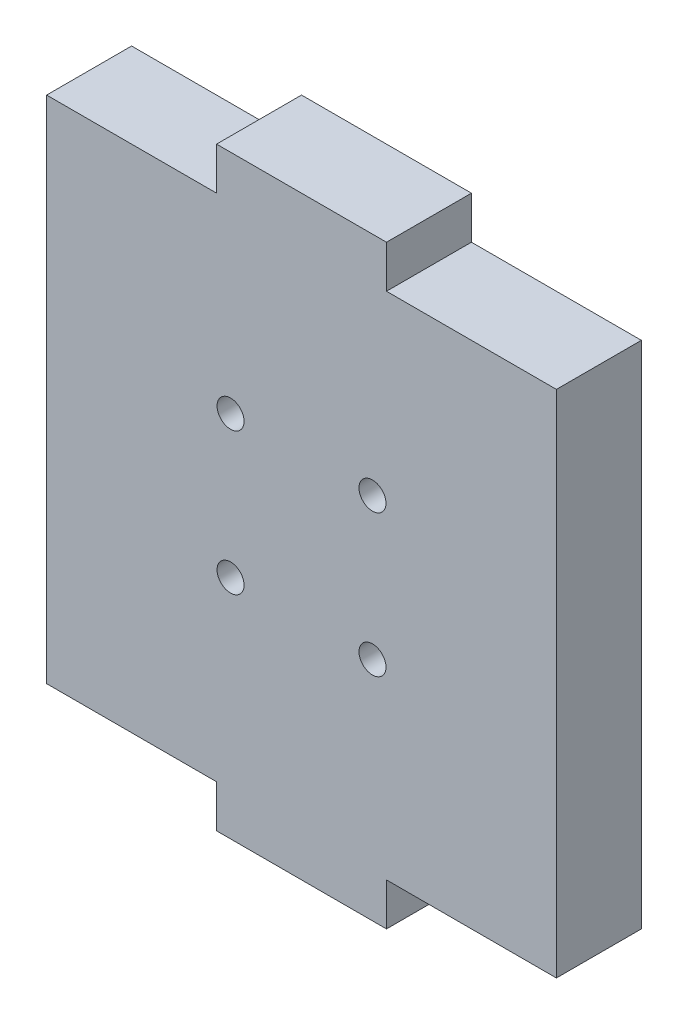
SolidWorks part; units mm, degrees
material "7050-T73510"
ref_plane "Front Plane" through (0, 0, 0) normal (0, 0, 1) x (1, 0, 0)
ref_plane "Top Plane" through (0, 0, 0) normal (0, 1, 0) x (1, 0, 0)
ref_plane "Right Plane" through (0, 0, 0) normal (1, 0, 0) x (0, 0, -1)
sketch "Sketch1" plane through (0, 0, 0) normal (0, 0, 1) x (1, 0, 0)
  line L0 (55, 0) -> (-55, 0) construction
  line L1 (-38.1, -38.1) -> (38.1, -38.1)
  line L2 (-38.1, -38.1) -> (-38.1, 38.1)
  line L3 (-38.1, 38.1) -> (38.1, 38.1)
  line L4 (38.1, -38.1) -> (38.1, 38.1)
  line L5 (-38.1, -38.1) -> (38.1, 38.1) construction
  line L6 (-38.1, 38.1) -> (38.1, -38.1) construction
  line L7 (-12.7, 38.1) -> (12.7, 38.1)
  line L8 (-12.7, 38.1) -> (-12.7, 44.45)
  line L9 (-12.7, 44.45) -> (12.7, 44.45)
  line L10 (12.7, 38.1) -> (12.7, 44.45)
  line L11 (-12.7, -44.45) -> (12.7, -44.45)
  line L12 (12.7, -38.1) -> (12.7, -44.45)
  line L13 (-12.7, -38.1) -> (12.7, -38.1)
  line L14 (-12.7, -38.1) -> (-12.7, -44.45)
  point P0 (0, 0)
  point P10 (0, 44.45)
  point P11 (0, 38.1)
  point P18 (0, -38.1)
  point P19 (0, -44.45)
  dimension "D1" = 76.2
  dimension "D2" = 76.2
  dimension "D3" = 25.4
  dimension "D4" = 6.35
extrude "Boss-Extrude1" add sketch "Sketch1" along normal blind 12.7 contours L1 L4 L3 L2 | L1 L14 L11 L12 | L3 L10 L9 L8 region at (0, 0, 0) region at (0, -41.275, 0) region at (0, 41.275, 0)
sketch "Sketch2" plane through (0, 0, 12.7) normal (0, 0, 1) x (1, 0, 0)
  line L0 (55, 0) -> (-55, 0) construction
  line L1 (-10.6066, -10.6066) -> (10.6066, -10.6066)
  line L2 (-10.6066, -10.6066) -> (-10.6066, 10.6066)
  line L3 (-10.6066, 10.6066) -> (10.6066, 10.6066)
  line L4 (10.6066, -10.6066) -> (10.6066, 10.6066)
  line L5 (-10.6066, -10.6066) -> (10.6066, 10.6066) construction
  line L6 (-10.6066, 10.6066) -> (10.6066, -10.6066) construction
  line L7 (0, -55) -> (0, 55) construction
  circle A0 centre (10.6066, 10.6066) radius 2.0193
  circle A1 centre (10.6066, -10.6066) radius 2.0193
  circle A2 centre (-10.6066, -10.6066) radius 2.0193
  circle A3 centre (-10.6066, 10.6066) radius 2.0193
  point P0 (0, 0)
  dimension "D2" = 4.0386
  dimension "D1" = 30
extrude "Cut-Extrude1" cut sketch "Sketch2" against normal through all contours A3 | A0 | A1 | A2
